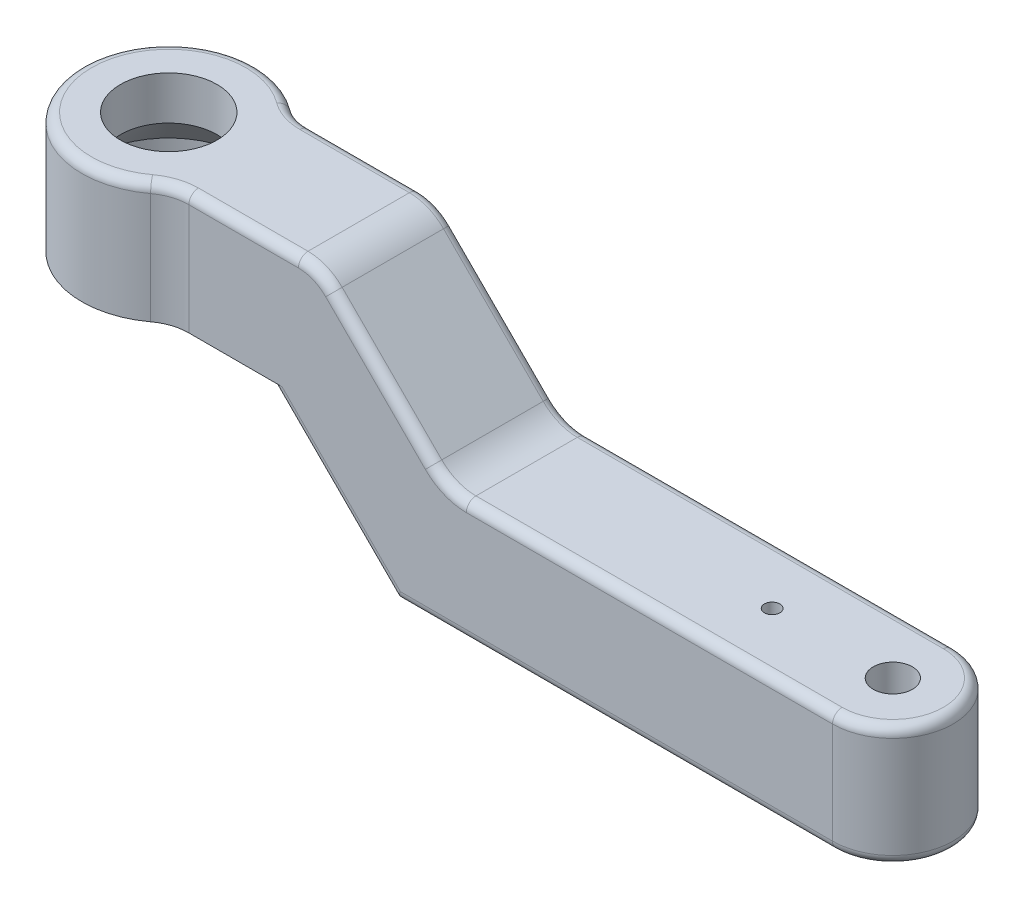
SolidWorks part; units mm, degrees
ref_plane "Alzado" through (0, 0, 0) normal (0, 0, 1) x (1, 0, 0)
ref_plane "Planta" through (0, 0, 0) normal (0, 1, 0) x (1, 0, 0)
ref_plane "Vista lateral" through (0, 0, 0) normal (1, 0, 0) x (0, 0, -1)
sketch "Croquis1" plane through (0, 0, 0) normal (0, 1, 0) x (1, 0, 0)
  line L0 (-75, 0) -> (75, 0) construction
  line L1 (75, -12.5) -> (-58.3342, -12.5)
  line L3 (75, 12.5) -> (-58.3342, 12.5)
  arc A1 (75, -12.5) -> (75, 12.5) centre (75, 0) ccw
  arc A2 (-64.2863, 14.4643) -> (-64.2863, -14.4643) centre (-75, 0) ccw
  arc A3 (-58.3342, -12.5) -> (-64.2863, -14.4643) centre (-58.3342, -22.5) ccw
  arc A4 (-58.3342, 12.5) -> (-64.2863, 14.4643) centre (-58.3342, 22.5) cw
  point P0 (0, 0)
  dimension "D3" = 36
  dimension "D4" = 10
  dimension "D1" = 25
  dimension "D2" = 150
extrude "Saliente-Extruir1" add sketch "Croquis1" along normal blind 51.5
ref_axis "Eje1" through (75, 51.5, 0) along (0, -1, 0)
ref_axis "Eje2" through (-75, 51.5, 0) along (0, -1, 0)
sketch "Croquis3" plane through (0, 0, 0) normal (0, 0, 1) x (1, 0, 0)
  line L0 (-58.3342, 0) -> (75, 0) construction
  line L1 (87.5, 25) -> (-5, 25)
  line L2 (-5, 25) -> (-31.5, 51.5)
  line L3 (-58.3342, 51.5) -> (75, 51.5) construction
  line L4 (-31.5, 51.5) -> (87.5, 51.5)
  line L5 (87.5, 51.5) -> (87.5, 25)
  line L6 (-15.3553, 0) -> (-41.8553, 26.5)
  line L7 (-41.8553, 26.5) -> (-93, 26.5)
  line L8 (-93, 51.5) -> (-93, 0) construction
  line L9 (-93, 26.5) -> (-93, 0)
  line L10 (-93, 0) -> (-15.3553, 0)
  line L11 (-64.2863, 51.5) -> (-93, 51.5) construction
  line L12 (-75, 51.5) -> (-75, 0) construction
  line L13 (75, 51.5) -> (75, 0) construction
  dimension "D1" = 25
  dimension "D2" = 25
  dimension "D3" = 80
  dimension "D4" = 43.5
  dimension "D5" = 25
extrude "Cortar-Extruir2" cut sketch "Croquis3" against normal mid plane 51.5
sketch "Croquis4" plane through (0, 0, 0) normal (0, 0, 1) x (1, 0, 0)
  line L0 (-75, 26.5) -> (-75, 51.5)
  line L1 (-75, 51.5) -> (-75, 0) construction
  line L2 (-93, 26.5) -> (-64.2863, 26.5) construction
  line L3 (-64.2863, 51.5) -> (-93, 51.5) construction
  line L4 (-75, 51.5) -> (-85, 51.5)
  line L5 (-85, 51.5) -> (-85, 42.5)
  line L6 (-85, 42.5) -> (-91.1, 35.5)
  line L7 (-91.1, 35.5) -> (-91.1, 26.5)
  line L8 (-91.1, 26.5) -> (-75, 26.5)
  line L9 (-75, 26.5) -> (-75.2427, 26.5411)
  dimension "D1" = 16.1
  dimension "D2" = 10
  dimension "D3" = 9
  dimension "D4" = 9
revolve "Cortar-Revolución1" cut sketch "Croquis4" angle 360 about L0
sketch "Croquis5" plane through (0, 0, 0) normal (0, 1, 0) x (1, 0, 0)
  circle A0 centre (75, 0) radius 4.05
  circle A1 centre (50, 0) radius 1.6
  dimension "D1" = 8.1
  dimension "D2" = 3.2
  dimension "D3" = 25
extrude "Cortar-Extruir3" cut sketch "Croquis5" along normal through all
fillet "Redondeo1" radius 10 2 edges at (-31.5, 51.5, 0) (-5, 25, 0)
fillet "Redondeo2" radius 2 14 edges at (-4.6847, 25.7612, -12.5) (-18.25, 38.25, -12.5) (-31.8153, 50.7388, -12.5) (-46.9882, 51.5, -12.5) (-61.4681, 51.5, -13.0038) (-93, 51.5, 0) (-61.4681, 51.5, 13.0038) (-46.9882, 51.5, 12.5) (-31.8153, 50.7388, 12.5) (-18.25, 38.25, 12.5) (-4.6847, 25.7612, 12.5) (37.0711, 25, 12.5) (87.5, 25, 0) (37.0711, 25, -12.5)
fillet "Redondeo3" radius 2 5 edges at (29.8223, 0, 12.5) (87.5, 0, 0) (-28.6053, 13.25, 12.5) (-28.6053, 13.25, -12.5) (29.8223, 0, -12.5)
